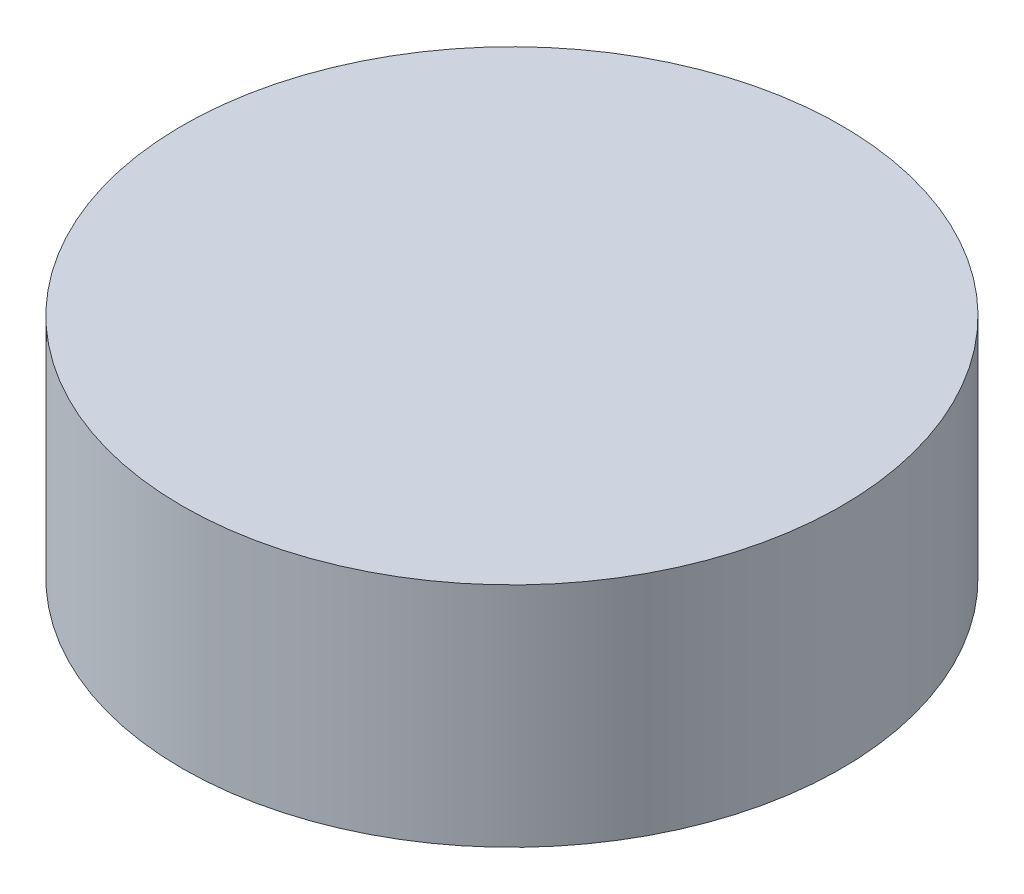
SolidWorks part; units mm, degrees
ref_plane "Front Plane" through (0, 0, 0) normal (0, 0, 1) x (1, 0, 0)
ref_plane "Top Plane" through (0, 0, 0) normal (0, 1, 0) x (1, 0, 0)
ref_plane "Right Plane" through (0, 0, 0) normal (1, 0, 0) x (0, 0, -1)
sketch "Sketch1" plane through (0, 0, 0) normal (0, 1, 0) x (1, 0, 0)
  circle A0 centre (0, 0) radius 36.83
  dimension "D1" = 73.66
extrude "Boss-Extrude1" add sketch "Sketch1" along normal blind 25.4
ref_axis "Axis1" through (0, -1.27, 0) along (0, 1, 0)
